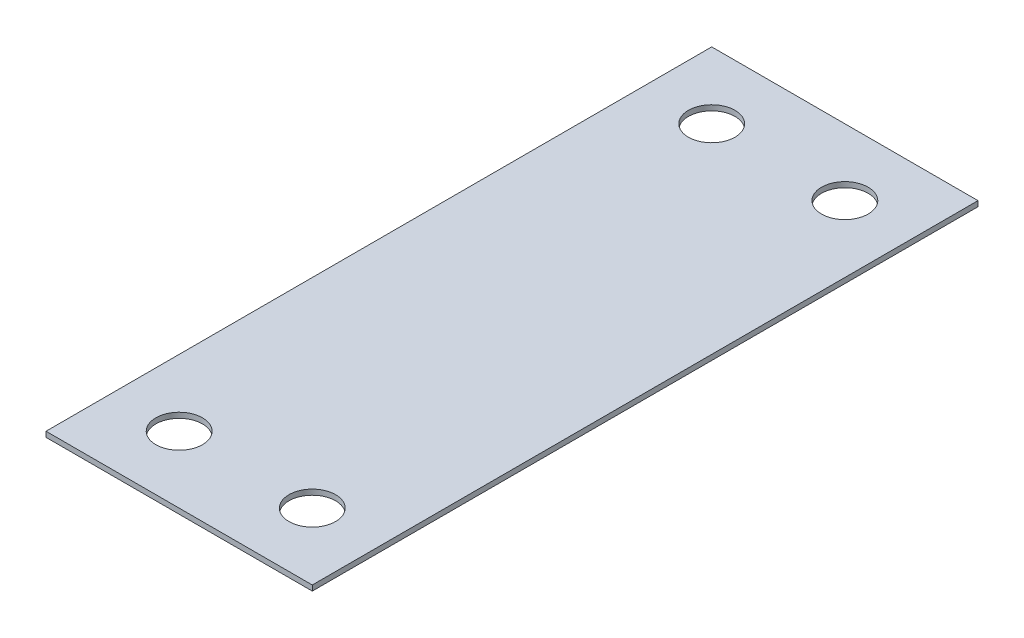
SolidWorks part; units mm, degrees
ref_plane "Front Plane" through (0, 0, 0) normal (0, 0, 1) x (1, 0, 0)
ref_plane "Top Plane" through (0, 0, 0) normal (0, 1, 0) x (1, 0, 0)
ref_plane "Right Plane" through (0, 0, 0) normal (1, 0, 0) x (0, 0, -1)
sketch "Sketch1" plane through (0, 0, 0) normal (0, 1, 0) x (1, 0, 0)
  line L0 (0, 0) -> (20, 0)
  line L1 (20, 0) -> (20, 10)
  line L2 (20, 10) -> (20, 40)
  line L3 (20, 40) -> (20, 50)
  line L4 (20, 50) -> (0, 50)
  line L5 (0, 50) -> (0, 0)
  line L6 (10, 50) -> (10, 0) construction
  line L7 (20, 25) -> (0, 25) construction
  circle A0 centre (5, 45) radius 1.75
  circle A1 centre (15, 45) radius 1.75
  circle A2 centre (15, 5) radius 1.75
  circle A3 centre (5, 5) radius 1.75
  dimension "D5" = 3.5
  dimension "D1" = 20
  dimension "D2" = 10
  dimension "D3" = 10
  dimension "D4" = 30
  dimension "D6" = 5
  dimension "D7" = 5
  dimension "D8" = 5
extrude "Boss-Extrude1" add sketch "Sketch1" along normal blind 0.4
equation "\"length\" =30"
equation "\"D4@Sketch1\"=\"length\""
equation "\"top_length\" =10"
equation "\"D3@Sketch1\"=\"top_length\""
